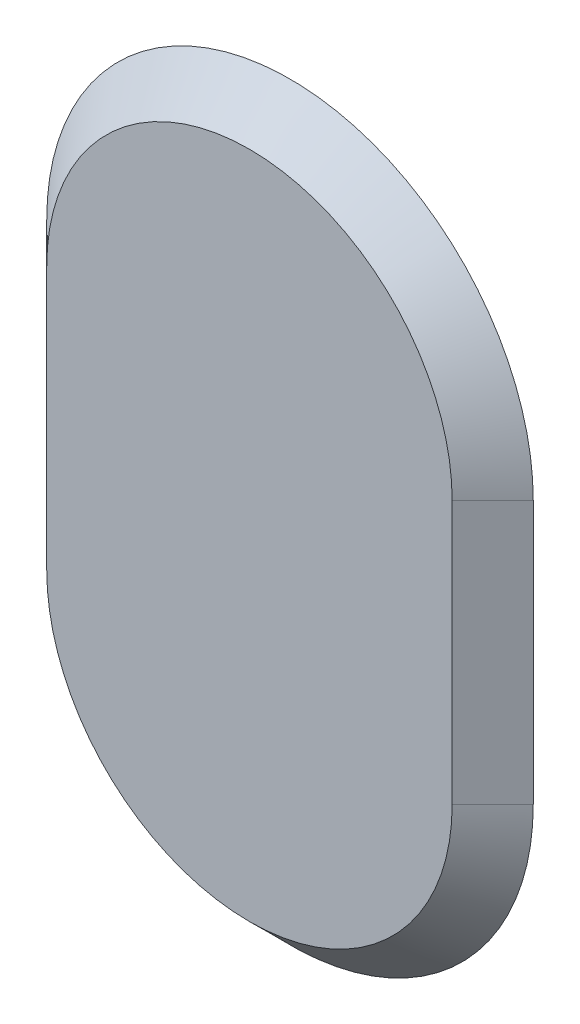
SolidWorks part; units mm, degrees
ref_plane "Alzado" through (0, 0, 0) normal (0, 0, 1) x (1, 0, 0)
ref_plane "Planta" through (0, 0, 0) normal (0, 1, 0) x (1, 0, 0)
ref_plane "Vista lateral" through (0, 0, 0) normal (1, 0, 0) x (0, 0, -1)
sketch "Croquis1" plane through (0, 0, 0) normal (0, 0, 1) x (1, 0, 0)
  line L0 (0, -3.25) -> (0, 3.25) construction
  line L1 (-6, -3.25) -> (-6, 3.25)
  line L2 (6, -3.25) -> (6, 3.25)
  arc A0 (-6, -3.25) -> (6, -3.25) centre (0, -3.25) ccw
  arc A1 (6, 3.25) -> (-6, 3.25) centre (0, 3.25) ccw
  point P2 (0, 0)
  point P8 (0, 9.25)
  point P9 (0, -9.25)
  dimension "D1" = 12
  dimension "D2" = 18.5
extrude "Saliente-Extruir1" add sketch "Croquis1" along normal blind 1
chamfer "Chaflán1" distance 1 angle 45 4 edges at (0, -9.25, 1) (6, 0, 1) (-6, 0, 1) (0, 9.25, 1)
